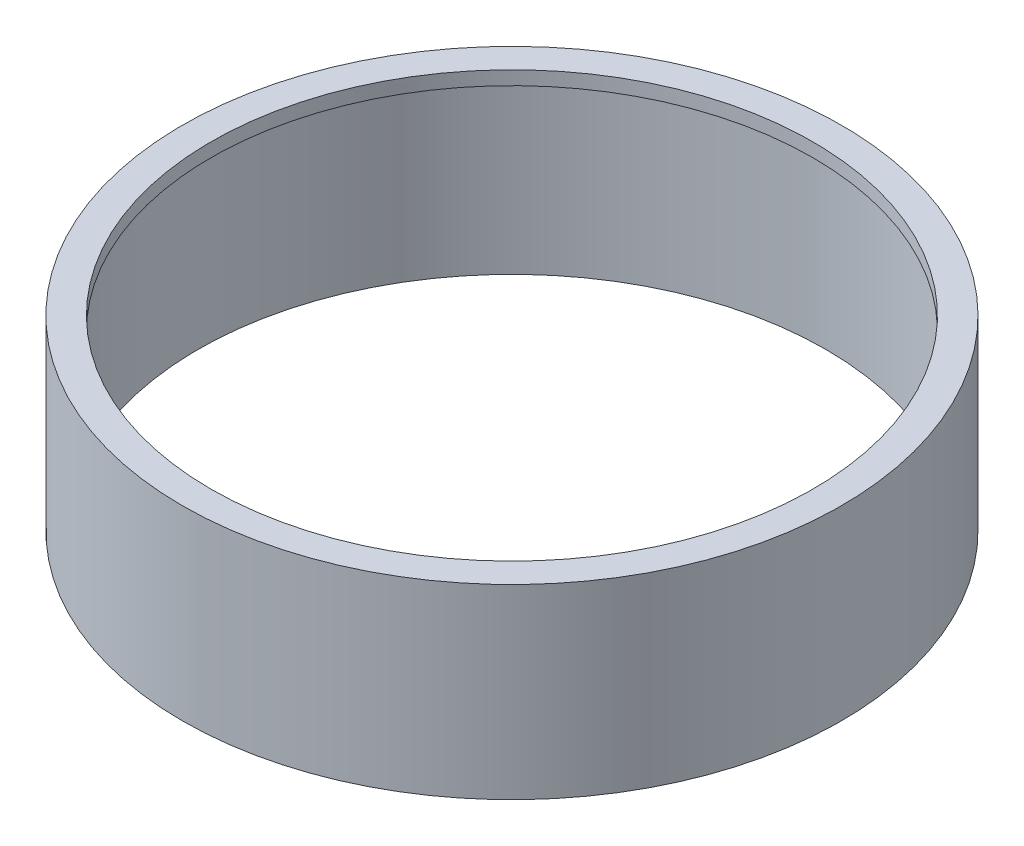
SolidWorks part; units mm, degrees
ref_plane "Front Plane" through (0, 0, 0) normal (0, 0, 1) x (1, 0, 0)
ref_plane "Top Plane" through (0, 0, 0) normal (0, 1, 0) x (1, 0, 0)
ref_plane "Right Plane" through (0, 0, 0) normal (1, 0, 0) x (0, 0, -1)
sketch "Sketch1" plane through (0, 0, 0) normal (0, 1, 0) x (1, 0, 0)
  circle A0 centre (0, 0) radius 40.005
  dimension "D1" = 80.01
extrude "Boss-Extrude1" add sketch "Sketch1" along normal blind 22.62 contours A0
sketch "Sketch3" plane through (0, 0, 0) normal (0, -1, 0) x (-1, 0, 0)
  circle A0 centre (0, 0) radius 38.1
  dimension "D1" = 76.2
extrude "Cut-Extrude1" cut sketch "Sketch3" against normal blind 20.95
sketch "Sketch4" plane through (0, 22.62, 0) normal (0, 1, 0) x (1, 0, 0)
  circle A0 centre (0, 0) radius 36.525
  dimension "D1" = 73.05
extrude "Cut-Extrude2" cut sketch "Sketch4" against normal through all
equation "\"ODia\"= 3.15in"
equation "\"IDia\"= 3in"
equation "\"InnerLength\"= 20.95mm"
equation "\"OutterLength\"= 22.62mm"
equation "\"LIpDia\"= 73.05mm"
